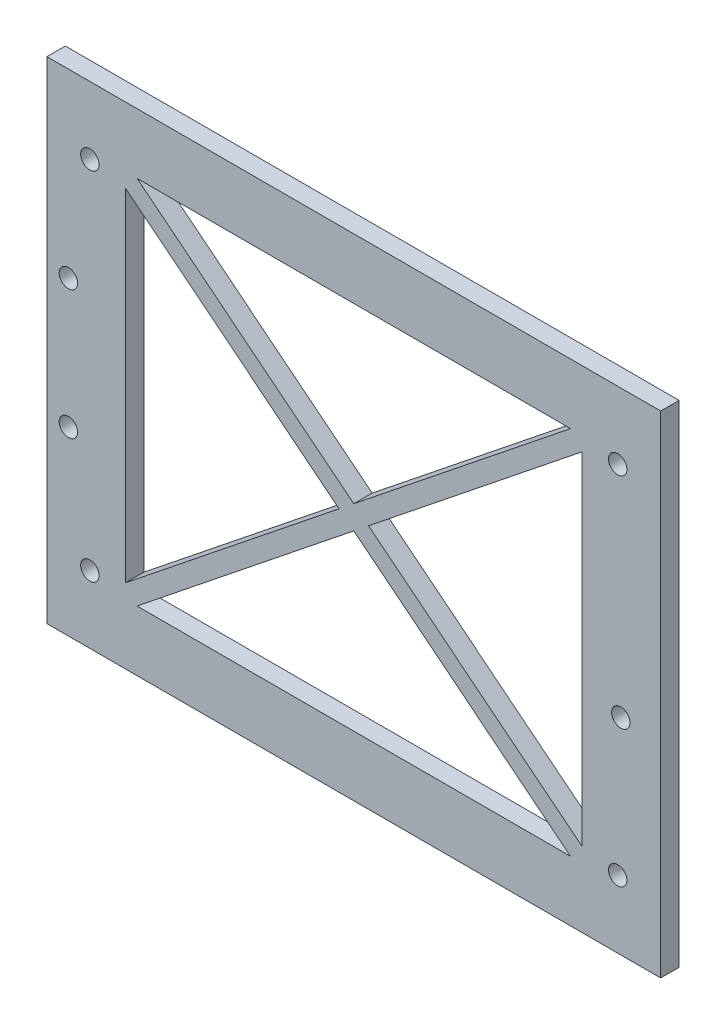
SolidWorks part; units mm, degrees
ref_plane "前视基准面" through (0, 0, 0) normal (0, 0, 1) x (1, 0, 0)
ref_plane "上视基准面" through (0, 0, 0) normal (0, 1, 0) x (1, 0, 0)
ref_plane "右视基准面" through (0, 0, 0) normal (1, 0, 0) x (0, 0, -1)
sketch "草图1" plane through (0, 0, 0) normal (0, 0, 1) x (1, 0, 0)
  line L0 (-50, 0) -> (50, 0) construction
  line L1 (50, -40) -> (-50, -40)
  line L2 (50, -40) -> (50, 40)
  line L3 (50, 40) -> (-50, 40)
  line L4 (-50, -40) -> (-50, 40)
  line L5 (50, -40) -> (-50, 40) construction
  line L6 (50, 40) -> (-50, -40) construction
  line L7 (-46.5, 10.5) -> (-46.5, -10.5)
  line L8 (0, -40) -> (0, 40) construction
  line L9 (0, 0) -> (36.25, -29)
  line L10 (-36.25, -29) -> (36.25, 29)
  line L11 (-36.25, 29) -> (36.25, -29) construction
  line L12 (-35.313, 30.1713) -> (0, 1.9209)
  line L13 (-37.187, 27.8287) -> (-2.4012, 0)
  line L14 (-36.25, -29) -> (36.25, 29) construction
  line L15 (-37.187, -27.8287) -> (-2.4012, 0)
  line L16 (-35.313, -30.1713) -> (0, -1.9209)
  line L17 (-37.187, 27.8287) -> (-37.187, -27.8287)
  line L18 (-35.313, 30.1713) -> (35.313, 30.1713)
  line L19 (-35.313, -30.1713) -> (35.313, -30.1713)
  line L20 (37.187, 27.8287) -> (37.187, -27.8287)
  line L21 (0, 1.9209) -> (35.313, 30.1713)
  line L22 (2.4012, 0) -> (37.187, 27.8287)
  line L23 (0, -1.9209) -> (35.313, -30.1713)
  line L24 (2.4012, 0) -> (37.187, -27.8287)
  circle A0 centre (-46.5, 10.5) radius 1.5
  circle A1 centre (-46.5, -10.5) radius 1.5
  circle A2 centre (43.5, -6.5) radius 1.5
  circle A3 centre (-43, 29) radius 1.5
  circle A4 centre (43, 29) radius 1.5
  circle A5 centre (43, -29) radius 1.5
  circle A6 centre (-43, -29) radius 1.5
  arc A7 (-35.313, 30.1713) -> (-37.187, 27.8287) centre (-36.25, 29) ccw
  arc A8 (35.313, -30.1713) -> (37.187, -27.8287) centre (36.25, -29) ccw
  arc A9 (-37.187, -27.8287) -> (-35.313, -30.1713) centre (-36.25, -29) ccw
  arc A10 (37.187, 27.8287) -> (35.313, 30.1713) centre (36.25, 29) ccw
  point P0 (0, 0)
  point P28 (0, 0)
  point P33 (0, 0)
  dimension "D3" = 3
  dimension "D6" = 3
  dimension "D9" = 3
  dimension "D12" = 92.8453
  dimension "D16" = 70.6259
  dimension "D14" = 1.5
  dimension "D15" = 1.5
  dimension "D1" = 80
  dimension "D2" = 100
  dimension "D4" = 21
  dimension "D5" = 3.5
  dimension "D7" = 90
  dimension "D8" = 6.5
  dimension "D10" = 29
  dimension "D11" = 43
  dimension "D13" = 92.8453
  dimension "D17" = 55.6574
extrude "凸台-拉伸2" add sketch "草图1" along normal blind 3 contours L24 A8 L23 L16 A9 L15 L13 A7 L12 L21 A10 L22
extrude "凸台-拉伸3" add sketch "草图1<5>" along normal blind 3 contours L4 L1 L2 L3 A4 A3 A2 L16 L23 L24 L22 L21 L12 L13 L15 L17 L18 L20 L19 A1 A0 A5 A6 region at (0, -38.7194, 0)
sketch "草图1<5>" plane through (0, 0, 0) normal (0, 0, 1) x (1, 0, 0) same geometry as "草图1"
